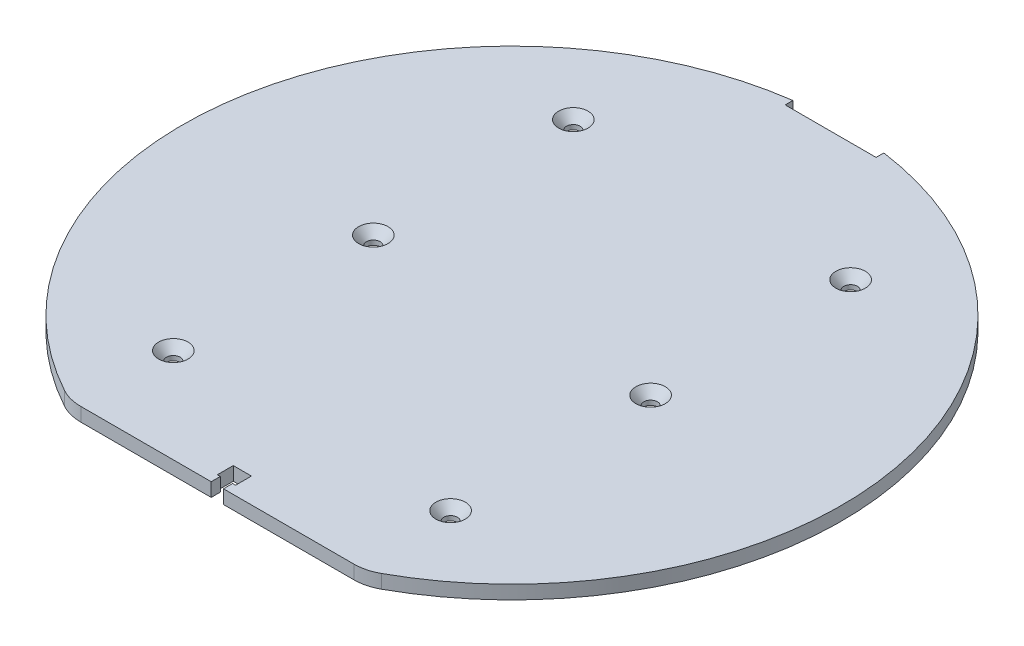
SolidWorks part; units mm, degrees
material "ABS"
ref_plane "Front Plane" through (0, 0, 0) normal (0, 0, 1) x (1, 0, 0)
ref_plane "Top Plane" through (0, 0, 0) normal (0, 1, 0) x (1, 0, 0)
ref_plane "Right Plane" through (0, 0, 0) normal (1, 0, 0) x (0, 0, -1)
sketch "Sketch1" plane through (0, 0, 0) normal (0, 1, 0) x (1, 0, 0)
  line L0 (0, -85) -> (0, 0) construction
  line L1 (30.03, -64.8129) -> (-30.03, -64.8129)
  arc A0 (34.8348, -63.5829) -> (-34.8348, -63.5829) centre (0, 0) ccw
  circle A1 centre (0, -85) radius 38.25 construction
  arc A2 (30.03, -64.8129) -> (34.8348, -63.5829) centre (30.03, -54.8129) ccw
  arc A3 (-30.03, -64.8129) -> (-34.8348, -63.5829) centre (-30.03, -54.8129) cw
  point P1 (40.2922, 60.2726)
  point P5 (0, -82.8008)
  point P12 (-32.4891, -64.8129)
  dimension "D1" = 145
  dimension "D3" = 76.5
  dimension "D4" = 10
  dimension "D2" = 85
extrude "Boss-Extrude1" add sketch "Sketch1" along normal blind 3
sketch "Sketch2" plane through (0, 3, 0) normal (0, 1, 0) x (1, 0, 0)
  line L1 (-30.5, -44) -> (30.5, -44) construction
  line L2 (-30.5, -44) -> (-30.5, 44) construction
  line L3 (-30.5, 44) -> (30.5, 44) construction
  line L4 (30.5, -44) -> (30.5, 44) construction
  line L5 (-30.5, -44) -> (30.5, 44) construction
  line L6 (-30.5, 44) -> (30.5, -44) construction
  circle A0 centre (-30.5, 44) radius 1.5
  circle A1 centre (30.5, 44) radius 1.5
  circle A2 centre (30.5, 0) radius 1.5
  circle A3 centre (30.5, -44) radius 1.5
  circle A4 centre (-30.5, -44) radius 1.5
  circle A5 centre (-30.5, 0) radius 1.5
  point P0 (0, 0)
  dimension "D3" = 3
  dimension "D1" = 61
  dimension "D2" = 88
extrude "Cut-Extrude1" cut sketch "Sketch2" against normal through all
chamfer "Chamfer1" distance 2 angle 41 6 edges at (30.5, 3, -42.5) (30.5, 3, 1.5) (30.5, 3, 45.5) (-30.5, 3, 45.5) (-30.5, 3, 1.5) (-30.5, 3, -42.5) first distance on face at (30.5, 0, -42.5) first distance on face at (30.5, 0, 1.5) first distance on face at (30.5, 0, 45.5) first distance on face at (-30.5, 0, 45.5) first distance on face at (-30.5, 0, 1.5) first distance on face at (-30.5, 0, -42.5)
sketch "Sketch3" plane through (0, 3, 0) normal (0, 1, 0) x (1, 0, 0)
  line L0 (-30.03, -64.8129) -> (30.03, -64.8129) construction
  line L1 (1.35, -62.8129) -> (2, -62.8129)
  line L2 (-2, -59.3129) -> (2, -59.3129)
  line L3 (-2, -59.3129) -> (-2, -62.8129)
  line L4 (-2, -62.8129) -> (-1.35, -62.8129)
  line L5 (2, -59.3129) -> (2, -62.8129)
  line L6 (-1.35, -64.8129) -> (1.35, -64.8129)
  line L7 (-1.35, -64.8129) -> (-1.35, -62.8129)
  line L9 (1.35, -64.8129) -> (1.35, -62.8129)
  point P10 (0, -64.8129)
  point P14 (0, -64.8129)
  dimension "D1" = 2.7
  dimension "D2" = 4
  dimension "D3" = 3.5
  dimension "D4" = 2
extrude "Cut-Extrude2" cut sketch "Sketch3" against normal through all
sketch "Sketch4" plane through (0, 3, 0) normal (0, 1, 0) x (1, 0, 0)
  line L1 (-10, 71.807) -> (10, 71.807)
  line L2 (-10, 71.807) -> (-10, 70.107)
  line L3 (-10, 70.107) -> (10, 70.107)
  line L4 (10, 71.807) -> (10, 70.107)
  arc A0 (34.8348, -63.5829) -> (-34.8348, -63.5829) centre (0, 0) ccw construction
  point P7 (20.3409, 69.5881)
  dimension "D1" = 1.7
  dimension "D2" = 20
extrude "Cut-Extrude3" cut sketch "Sketch4" against normal through all
equation "\"smallPulleyTeeth\"= 30"
equation "\"largePulleyTeeth\"= 30"
equation "\"eighthThick\"= 3.0mm"
equation "\"sixteenthThick\" = 1.7mm"
equation "\"quarterThick\"=6.0mm"
equation "\"OD\" = 145mm"
equation "\"puckAngle\" = 60.5deg"
equation "\"puckDiam\" = 76.5mm"
equation "\"puckDist\" = 85mm"
equation "\"scoopFillet\" = 5mm"
equation "\"axlePress\" = 5.9mm"
equation "\"press\" = 0.2mm"
equation "\"wheelClear\" = 0.3mm"
equation "\"10-32clear\" = 4.8mm"
equation "\"10-32tap\" = 4.45mm"
equation "\"6-32clear\" = 3.3mm"
equation "\"8-32clear\" = 4.0mm"
equation "\"4-40clear\" = 3.0mm"
equation "\"wheelHeight\" = 22mm"
equation "\"wheelWell\" = 65mm"
equation "\"ledSmall\" = 3.1mm"
equation "\"ledLarge\" = 4.2mm"
equation "\"ledLength\" = 4.2mm"
equation "\"D1@Sketch1\"=\"OD\""
equation "\"D1@Boss-Extrude1\"=\"eighthThick\""
equation "\"D3@Sketch2\"=\"4-40clear\""
equation "\"D3@Sketch1\"=\"puckDiam\""
equation "\"D2@Sketch1\"=\"puckDist\""
equation "\"4-40close\" = 2.7mm"
equation "\"4-40nutThick\" = 2.2mm"
equation "\"4-40nutWidth\" = 6.2mm"
equation "\"D1@Sketch4\"=\"sixteenthThick\""
equation "\"D1@Sketch3\"=\"4-40close\""
equation "\"4-40insertHeight\" = 3.5mm"
equation "\"4-40insert\" = 4mm"
equation "\"D2@Sketch3\"=\"4-40insert\""
equation "\"D3@Sketch3\"=\"4-40insertHeight\""
